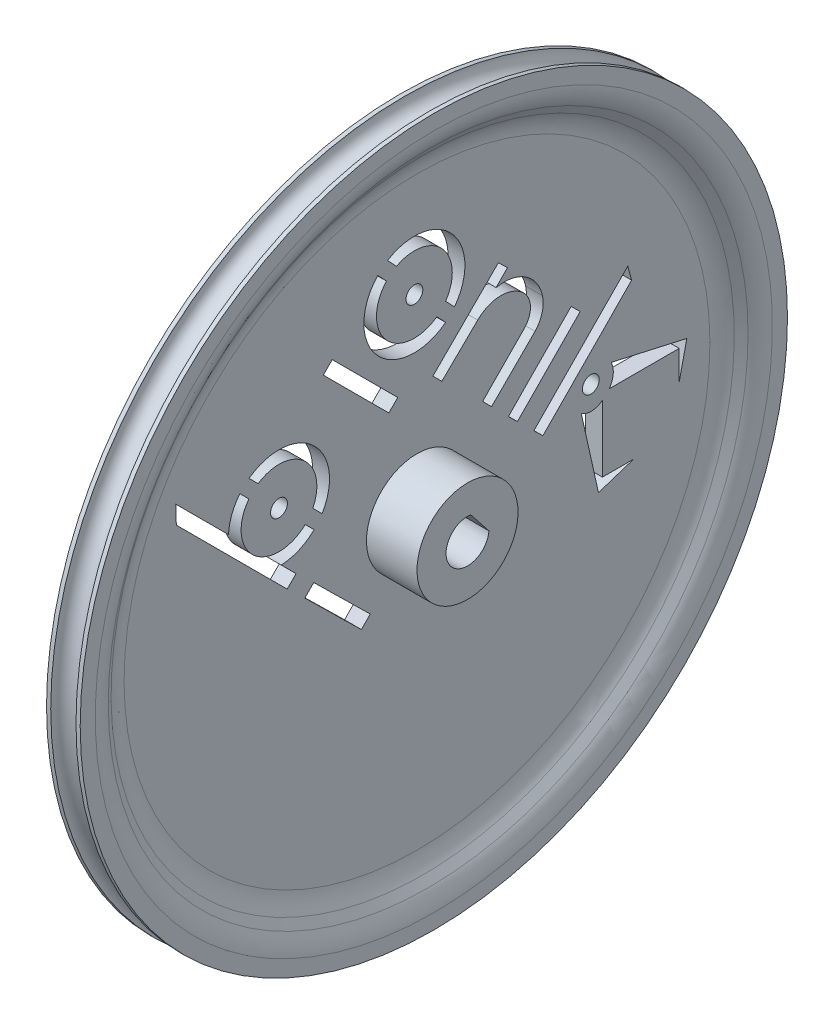
SolidWorks part; units mm, degrees
ref_plane "Płaszczyzna przednia" through (0, 0, 0) normal (0, 0, 1) x (1, 0, 0)
ref_plane "Płaszczyzna górna" through (0, 0, 0) normal (0, 1, 0) x (1, 0, 0)
ref_plane "Płaszczyzna prawa" through (0, 0, 0) normal (1, 0, 0) x (0, 0, -1)
sketch "Szkic1" plane through (0, 0, 0) normal (0, 0, 1) x (1, 0, 0)
  line L0 (6, -12.7789) -> (-2, -12.7789)
  line L1 (6, -12.7789) -> (6, -6.7789)
  line L2 (6, -6.7789) -> (0, -6.7789)
  line L3 (0, -6.7789) -> (0, 22.01)
  line L4 (2, 29.2211) -> (1.5, 29.2211)
  line L5 (2, 29.2211) -> (2, 27.4322)
  line L6 (-1.5, 29.2211) -> (-2, 29.2211)
  line L9 (-2, 29.2211) -> (-2, -12.7789)
  line L10 (0.6718, 24.2288) -> (1.3282, 25.2134)
  arc A0 (1.5, 29.2211) -> (-1.5, 29.2211) centre (0, 29.2211) cw
  arc A1 (2, 27.4322) -> (1.3282, 25.2134) centre (-2, 27.4322) cw
  arc A2 (0, 22.01) -> (0.6718, 24.2288) centre (4, 22.01) cw
  point P10 (2, 26.2211)
  point P17 (0, 23.2211)
  dimension "D6" = 1.5
  dimension "D9" = 4
  dimension "D10" = 4
  dimension "D1" = 8
  dimension "D2" = 6
  dimension "D3" = 42
  dimension "D4" = 4
  dimension "D5" = 3
  dimension "D7" = 0.5
  dimension "D8" = 30
  dimension "D11" = 2
revolve "Obrót1" add sketch "Szkic1" angle 360 about L0
sketch "Szkic4" plane through (6, 0, 0) normal (1, 0, 0) x (0, 0, -1)
  line L0 (0.3809, -10.2575) -> (2.5412, -12.9904)
  arc A0 (0.3809, -10.2575) -> (2.5412, -12.9904) centre (0, -12.7789) ccw
  circle A2 centre (0, -12.7789) radius 6 construction
extrude "Wytnij-wyciągnięcie8" cut sketch "Szkic4" against normal through all
sketch "Szkic5" plane through (0, 0, 0) normal (1, 0, 0) x (0, 0, -1)
  line L0 (112.1629, 275.1146) -> (679.4962, 275.1146) construction
  line L1 (-28.5833, 0.1628) -> (-15.4205, -13)
  line L2 (-15.4205, -13) -> (-14.3598, -11.9393)
  line L3 (-14.3598, -11.9393) -> (-16.128, -10.1712)
  line L4 (-22.3853, -3.9139) -> (-28.6529, 2.3537)
  line L5 (-28.6529, 2.3537) -> (-28.5833, 0.1628)
  line L6 (-11.1247, 6.8611) -> (-10.0641, 7.9218)
  line L7 (-10.0641, 7.9218) -> (-2.2859, 0.1436)
  line L8 (-2.2859, 0.1436) -> (-3.3466, -0.917)
  line L9 (-3.3466, -0.917) -> (-11.1247, 6.8611)
  line L10 (2.9478, -0.8115) -> (1.8871, 0.2492)
  line L11 (1.8871, 0.2492) -> (9.6653, 8.0274)
  line L12 (9.6653, 8.0274) -> (10.74, 6.9809)
  line L13 (10.74, 6.9809) -> (9.3969, 5.6017)
  line L14 (2.9478, -0.8115) -> (7.2101, 3.3578)
  line L15 (14.0203, -1.204) -> (8.8534, -6.3709)
  line L16 (8.8534, -6.3709) -> (7.7928, -5.3103)
  line L17 (7.7928, -5.3103) -> (12.7237, -0.2884)
  line L18 (18.3075, -0.7969) -> (19.3778, -1.8478)
  line L19 (19.3778, -1.8478) -> (11.9244, -9.4388)
  line L20 (11.9244, -9.4388) -> (10.8541, -8.3878)
  line L21 (10.8541, -8.3878) -> (18.3075, -0.7969)
  line L22 (13.8806, -11.3595) -> (25.0288, -0.0056)
  line L23 (25.0288, -0.0056) -> (25.4882, -1.6787)
  line L24 (25.4882, -1.6787) -> (14.9509, -12.4104)
  line L25 (14.9509, -12.4104) -> (13.8806, -11.3595)
  line L26 (-13.316, -14.9733) -> (-12.2651, -13.903)
  line L27 (-12.2651, -13.903) -> (-5.5501, -20.4964)
  line L28 (-5.5501, -20.4964) -> (-6.601, -21.5667)
  line L29 (-6.601, -21.5667) -> (-13.316, -14.9733)
  line L30 (23.0696, -8.9276) -> (32.0451, -10.9511)
  line L31 (32.0451, -10.9511) -> (31.1382, -14.9733)
  line L32 (31.1382, -14.9733) -> (31.1382, -11.5167)
  line L33 (31.1382, -11.5167) -> (22.8358, -11.5167)
  line L34 (19.5102, -12.4086) -> (21.5532, -21.5667)
  line L35 (21.5532, -21.5667) -> (25.7129, -20.206)
  line L36 (25.7129, -20.206) -> (22.0216, -20.206)
  line L37 (22.0216, -20.206) -> (22.0216, -12.291)
  line L38 (-12.217, -8.4872) -> (-13.2779, -7.4263)
  line L39 (-11.2736, -7.3093) -> (-12.3753, -6.2076)
  line L40 (-19.9685, -1.4471) -> (-21.0363, -0.3794)
  line L41 (-18.8718, -0.4225) -> (-19.9488, 0.6545)
  line L42 (-2.4343, 13.7136) -> (-3.4985, 14.8293)
  line L43 (-3.6256, 12.7892) -> (-4.6626, 13.8765)
  line L44 (3.3987, 7.1983) -> (4.4508, 6.0952)
  line L45 (2.3542, 6.1201) -> (3.3959, 5.0279)
  arc A0 (-2.4343, 13.7136) -> (3.3987, 7.1983) centre (-0.3103, 9.7464) cw
  circle A1 centre (-16.3911, -4.177) radius 1
  arc A2 (-3.6256, 12.7892) -> (2.3542, 6.1201) centre (-0.3103, 9.7464) ccw
  circle A3 centre (-0.3103, 9.7464) radius 1
  arc A6 (7.2101, 3.3578) -> (12.7237, 3.3578) centre (9.9669, 0.601) cw
  arc A7 (9.3969, 5.6017) -> (14.901, 2.0136) centre (10.3549, 1.0556) cw
  arc A8 (12.7237, 3.3578) -> (12.7237, -0.2884) centre (10.9006, 1.5347) cw
  arc A9 (14.901, 2.0136) -> (14.0203, -1.204) centre (11.4227, 1.2362) cw
  circle A10 centre (20.6456, -9.9783) radius 1
  arc A11 (23.0696, -8.9276) -> (22.8358, -11.5167) centre (20.7483, -10.023) cw
  arc A12 (22.0216, -12.291) -> (19.5102, -12.4086) centre (20.6874, -10.674) cw
  arc A13 (-21.0363, -0.3794) -> (-22.3853, -3.9139) centre (-16.3911, -4.177) ccw
  arc A14 (-19.9488, 0.6545) -> (-11.2736, -7.3093) centre (-16.3911, -4.177) cw
  arc A15 (-12.3753, -6.2076) -> (-18.8718, -0.4225) centre (-16.3911, -4.177) ccw
  arc A16 (-19.9685, -1.4471) -> (-13.2779, -7.4263) centre (-16.3911, -4.177) ccw
  arc A17 (-12.217, -8.4872) -> (-16.128, -10.1712) centre (-16.3911, -4.177) cw
  arc A18 (-3.4985, 14.8293) -> (4.4508, 6.0952) centre (-0.3103, 9.7464) cw
  arc A19 (-4.6626, 13.8765) -> (3.3959, 5.0279) centre (-0.3103, 9.7464) ccw
  point P71 (0, -13)
  dimension "D4" = 1.5
  dimension "D11" = 1.5
  dimension "D12" = 2
  dimension "D13" = 2
  dimension "D14" = 1.5
  dimension "D15" = 1.5
  dimension "D19" = 11
  dimension "D23" = 1.5
  dimension "D24" = 1.5
  dimension "D25" = 6
  dimension "D26" = 6
  dimension "D1" = 1.5
  dimension "D2" = 1.5
  dimension "D3" = 1.5
  dimension "D5" = 1.5
  dimension "D6" = 1.5
  dimension "D7" = 1.5
  dimension "D8" = 1.5
  dimension "D9" = 1.5
  dimension "D10" = 1.5
  dimension "D16" = 1.5
  dimension "D17" = 1.5
  dimension "D18" = 1.5
  dimension "D20" = 11
  dimension "D21" = 10.6384
  dimension "D22" = 1.5
  dimension "D27" = 0.524
extrude "Wytnij-wyciągnięcie9" cut sketch "Szkic5" against normal through all
